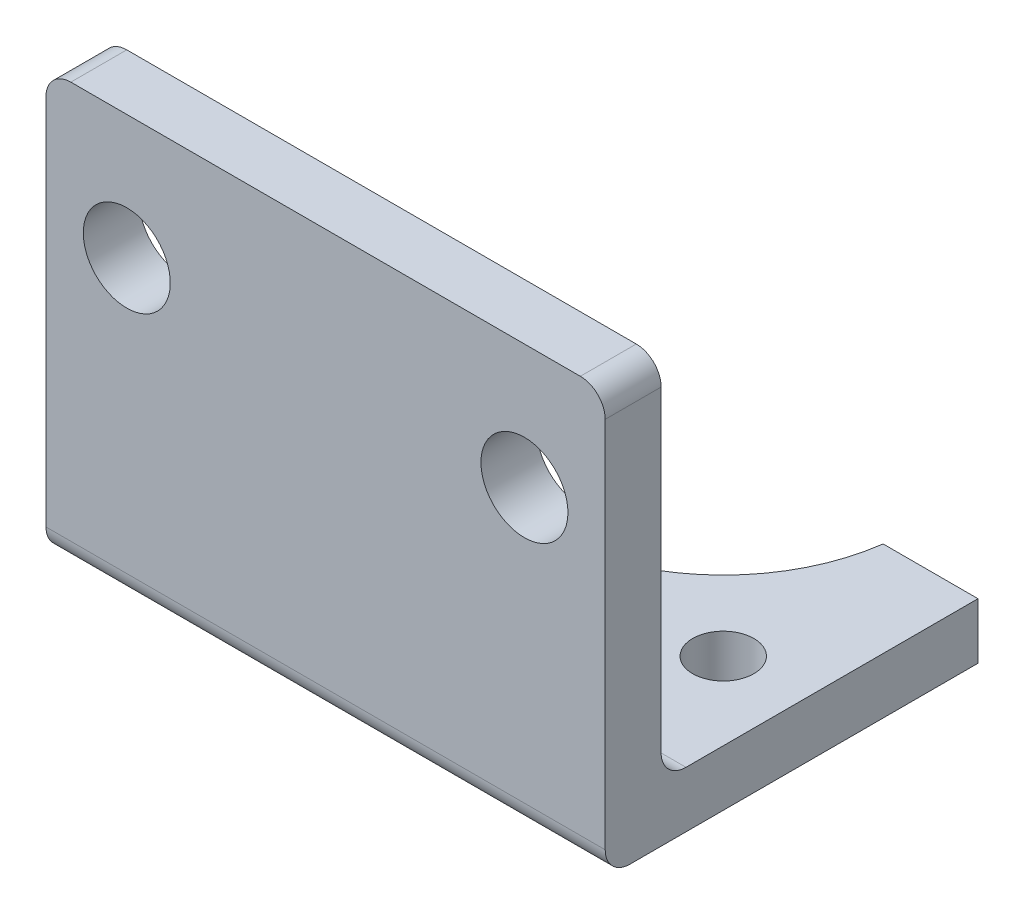
SolidWorks part; units mm, degrees
ref_plane "Alzado" through (0, 0, 0) normal (0, 0, 1) x (1, 0, 0)
ref_plane "Planta" through (0, 0, 0) normal (0, 1, 0) x (1, 0, 0)
ref_plane "Vista lateral" through (0, 0, 0) normal (1, 0, 0) x (0, 0, -1)
sketch "Croquis1" plane through (0, 0, 0) normal (0, 1, 0) x (1, 0, 0)
  line L0 (22.5, 0) -> (-22.5, 0)
  line L1 (-22.5, 0) -> (-22.5, 30)
  line L2 (-22.5, 30) -> (-14.8661, 30)
  line L3 (0, 8.25) -> (0, 0) construction
  line L4 (22.5, 30) -> (14.8661, 30)
  line L5 (22.5, 0) -> (22.5, 30)
  line L6 (-22.5, 30) -> (-22.5, 32) construction
  line L7 (-22.5, 32) -> (0, 32) construction
  line L8 (0, 0) -> (0, 17) construction
  circle A1 centre (-16.25, 15.75) radius 2.46
  circle A3 centre (16.25, 15.75) radius 2.46
  arc A6 (-15, 32) -> (14.8661, 30) centre (0, 32) ccw construction
  arc A7 (-14.8661, 30) -> (14.8661, 30) centre (0, 32) ccw
  point P7 (-22.5, 0)
  point P19 (22.5, 0)
  dimension "D3" = 2
  dimension "D4" = 4.92
  dimension "D7" = 16.25
  dimension "D8" = 16.25
  dimension "D1" = 22.5
  dimension "D2" = 30
  dimension "D5" = 22.5
  dimension "D6" = 17
extrude "Saliente-Extruir1" add sketch "Croquis1" along normal blind 4.5
sketch "Croquis2" plane through (0, 0, 0) normal (1, 0, 0) x (0, 0, -1)
  line L0 (0, 0) -> (4.5, 0)
  line L1 (0, 0) -> (30, 0) construction
  line L2 (4.5, 0) -> (4.5, 34)
  line L3 (4.5, 34) -> (0, 34)
  line L4 (0, 34) -> (0, 0)
  dimension "D1" = 4.5
  dimension "D2" = 34
extrude "Saliente-Extruir2" add sketch "Croquis2" along normal blind 22.5 and the other way blind 22.5
sketch "Croquis3" plane through (0, 0, -4.5) normal (0, 0, -1) x (-1, 0, 0)
  line L0 (22.5, 34) -> (-22.5, 34) construction
  circle A0 centre (-16, 24) radius 3.5
  circle A1 centre (16, 24) radius 3.5
  dimension "D1" = 7
  dimension "D2" = 32
  dimension "D3" = 10
  dimension "D4" = 16
extrude "Cortar-Extruir1" cut sketch "Croquis3" against normal blind 22.5
fillet "Redondeo1" radius 2 1 edges at (0, 0, 0)
fillet "Redondeo2" radius 2 1 edges at (0, 4.5, -4.5)
fillet "Redondeo3" radius 2 2 edges at (22.5, 34, -2.25) (-22.5, 34, -2.25)
